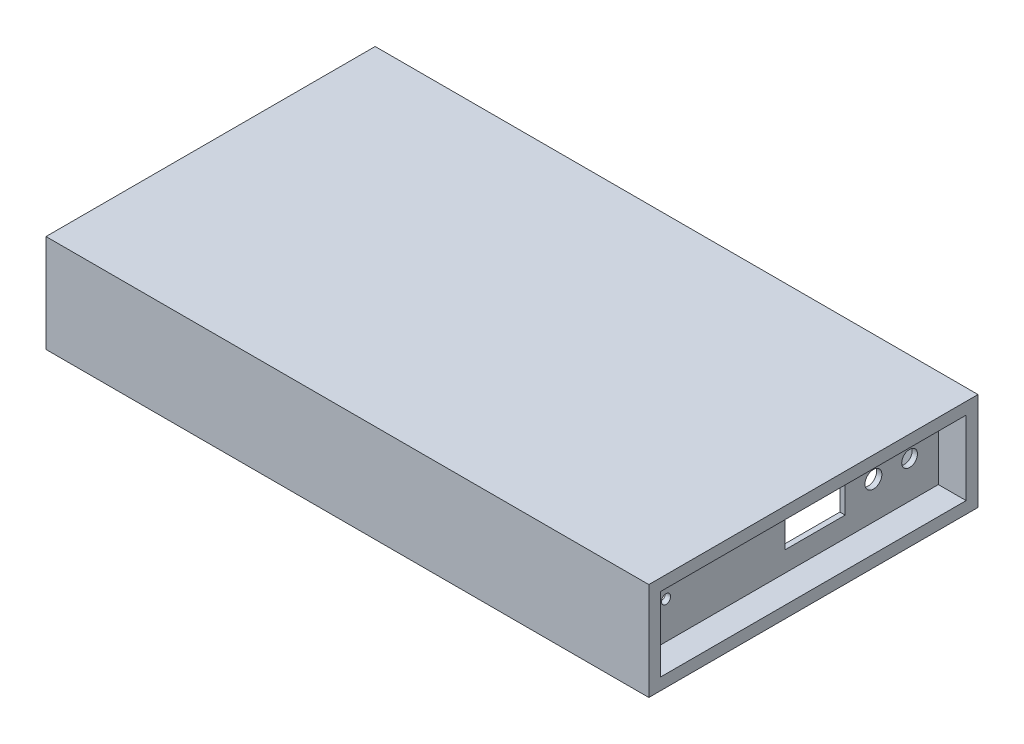
SolidWorks part; units mm, degrees
ref_plane "Front Plane" through (0, 0, 0) normal (0, 0, 1) x (1, 0, 0)
ref_plane "Top Plane" through (0, 0, 0) normal (0, 1, 0) x (1, 0, 0)
ref_plane "Right Plane" through (0, 0, 0) normal (1, 0, 0) x (0, 0, -1)
sketch "Sketch1" plane through (0, 0, 0) normal (0, 1, 0) x (1, 0, 0)
  line L0 (-228, -124.5) -> (-228, 124.5)
  line L1 (-219, -115.5) -> (219, -115.5)
  line L2 (-219, -115.5) -> (-219, 115.5)
  line L3 (-219, 115.5) -> (219, 115.5)
  line L4 (219, -115.5) -> (219, 115.5)
  line L5 (-219, -115.5) -> (219, 115.5) construction
  line L6 (-219, 115.5) -> (219, -115.5) construction
  line L7 (-228, 124.5) -> (228, 124.5)
  line L8 (228, -124.5) -> (228, 124.5)
  line L9 (-228, -124.5) -> (228, -124.5)
  point P0 (0, 0)
  dimension "D2" = 231
  dimension "D3" = 438
  dimension "D1" = 9
extrude "Boss-Extrude4" add sketch "Sketch1" along normal blind 9 contours L1 L4 L3 L2 | L0 L9 L8 L7 L4 L1 L2 L3 region at (-222.8045, 0, 0) region at (0, 0, 0)
extrude "Boss-Extrude5" add sketch "Sketch1<5>" against normal blind 65
sketch "Sketch1<5>" plane through (0, 0, 0) normal (0, 1, 0) x (1, 0, 0) same geometry as "Sketch1"
sketch "Sketch5" plane through (219, 0, 0) normal (-1, 0, 0) x (0, 0, 1)
  line L1 (-115.5, -65) -> (115.5, -65)
  line L2 (-115.5, -65) -> (-115.5, -56)
  line L3 (-115.5, -56) -> (115.5, -56)
  line L4 (115.5, 0) -> (-115.5, 0)
  line L5 (-115.5, 0) -> (-115.5, -65)
  line L6 (-115.5, -65) -> (115.5, -65)
  line L7 (115.5, -65) -> (115.5, 0)
  line L8 (115.5, 0) -> (-115.5, 0)
  line L9 (-115.5, 0) -> (-115.5, -65)
  line L10 (-115.5, -65) -> (115.5, -65)
  line L11 (115.5, -65) -> (115.5, 0)
  line L12 (115.5, -65) -> (115.5, -56)
  line M9 (115.5, 0) -> (-115.5, 0)
  line M10 (-115.5, 0) -> (-115.5, -65)
  line M11 (-115.5, -65) -> (115.5, -65)
  line M12 (115.5, -65) -> (115.5, 0)
  dimension "D2" = 9
  dimension "D3" = 56
  dimension "D1" = 0
extrude "Cut-Extrude1" cut sketch "Sketch5" against normal through all contours L3 M10 M12 M9 | L3 M10 M11 M12 region at (219, -60.5, 0) region at (219, -28, 0)
sketch "Sketch6" plane through (0, 0, 0) normal (0, -1, 0) x (1, 0, 0)
  line L0 (-219, 115.5) -> (219, 115.5) construction
  line L1 (207, 115.5) -> (203, 115.5)
  line L2 (207, 115.5) -> (207, -115.5)
  line L3 (207, -115.5) -> (203, -115.5)
  line L4 (203, 115.5) -> (203, -115.5)
  line L5 (-219, -115.5) -> (219, -115.5) construction
  line L7 (228, 124.5) -> (228, -124.5) construction
  dimension "D1" = 4
  dimension "D2" = 25
extrude "Boss-Extrude6" add sketch "Sketch6" along normal up to surface (65 mm away) up to face at (2.25, -65, 0)
extrude "Boss-Extrude7" add sketch "Sketch5<3>" along normal up to surface (12 mm away) from surface contours L3 M10 M11 M12 region at (219, -60.5, 0) up to face at (207, -32.5, 0) starting at face at (228, -30.25, 0)
sketch "Sketch5<3>" plane through (219, 0, 0) normal (-1, 0, 0) x (0, 0, 1) same geometry as "Sketch5"
sketch "Sketch7" plane through (207, 0, 0) normal (1, 0, 0) x (0, 0, -1)
  line L0 (-115.5, -28) -> (115.5, -28) construction
  line L2 (-0.5, -40.75) -> (45, -40.75)
  line L3 (-0.5, -40.75) -> (-0.5, -15.25)
  line L4 (-115.5, 0) -> (-115.5, -56)
  line L5 (-115.5, -56) -> (115.5, -56)
  line L6 (115.5, -56) -> (115.5, 0)
  line L7 (115.5, 0) -> (-115.5, 0)
  line L8 (-115.5, 0) -> (-115.5, -56) construction
  line L9 (-115.5, -56) -> (115.5, -56) construction
  line L10 (115.5, -56) -> (115.5, 0) construction
  line L11 (115.5, 0) -> (-115.5, 0) construction
  line L12 (-0.5, -15.25) -> (45, -15.25)
  line L13 (45, -40.75) -> (45, -15.25)
  line L14 (-0.5, -40.75) -> (45, -15.25) construction
  line L15 (-0.5, -15.25) -> (45, -40.75) construction
  circle A0 centre (-90.5, -28) radius 3.5
  circle A1 centre (66.4, -28) radius 6.4
  circle A2 centre (93.76, -28) radius 5.96
  point P6 (-20.5, -28)
  point P10 (22.25, -28)
  point P15 (60, -28)
  point P17 (72.8, -28)
  point P20 (87.8, -28)
  dimension "D2" = 7
  dimension "D8" = 12.8
  dimension "D10" = 11.92
  dimension "D3" = 25
  dimension "D4" = 70
  dimension "D5" = 20
  dimension "D6" = 45.5
  dimension "D7" = 25.5
  dimension "D9" = 15
  dimension "D11" = 15
  dimension "D1" = 0
extrude "Cut-Extrude2" cut sketch "Sketch7" against normal blind 150
sketch "Sketch8" plane through (207, 0, 0) normal (1, 0, 0) x (0, 0, -1)
  line L0 (-0.5, -15.25) -> (-0.5, -40.75) construction
  line L4 (-115.5, 0) -> (-115.5, -56)
  line L5 (-115.5, -56) -> (115.5, -56)
  line L6 (115.5, -56) -> (115.5, 0)
  line L7 (115.5, 0) -> (-115.5, 0)
  line L8 (-115.5, 0) -> (-115.5, -56)
  line L9 (-115.5, -56) -> (115.5, -56)
  line L10 (115.5, -56) -> (115.5, 0)
  line L11 (115.5, 0) -> (-115.5, 0)
  line L13 (-0.5, -15.25) -> (-0.5, -40.75)
  line L14 (45, -15.25) -> (-0.5, -15.25) construction
  line L15 (45, -40.75) -> (45, -15.25) construction
  line L16 (-0.5, -40.75) -> (45, -40.75) construction
  line L17 (45, -15.25) -> (-0.5, -15.25)
  line L18 (45, -40.75) -> (45, -15.25)
  line L19 (-0.5, -40.75) -> (45, -40.75)
  circle A0 centre (93.76, -28) radius 5.96 construction
  circle A1 centre (66.4, -28) radius 6.4 construction
  circle A2 centre (-90.5, -28) radius 3.5 construction
  circle A3 centre (93.76, -28) radius 5.96
  circle A4 centre (66.4, -28) radius 6.4
  circle A5 centre (-90.5, -28) radius 3.5
  dimension "D1" = 0
sketch "Sketch9" plane through (0, -65, 0) normal (0, -1, 0) x (1, 0, 0)
  line L8 (93, -50.5) -> (93, 50.5)
  line L25 (53, 90.5) -> (-154, 90.5)
  line L26 (-194, -50.5) -> (-194, 50.5)
  line L27 (53, -90.5) -> (-154, -90.5)
  line L29 (-228, 124.5) -> (228, 124.5)
  line L30 (-228, 124.5) -> (-228, -124.5)
  line L31 (-228, -124.5) -> (228, -124.5)
  line L32 (228, 124.5) -> (228, -124.5)
  arc A8 (93, 50.5) -> (53, 90.5) centre (53, 50.5) ccw
  arc A9 (93, -50.5) -> (53, -90.5) centre (53, -50.5) cw
  arc A10 (-194, -50.5) -> (-154, -90.5) centre (-154, -50.5) ccw
  arc A11 (-154, 90.5) -> (-194, 50.5) centre (-154, 50.5) ccw
  dimension "D2" = 40
  dimension "D5" = 181
  dimension "D6" = 287
